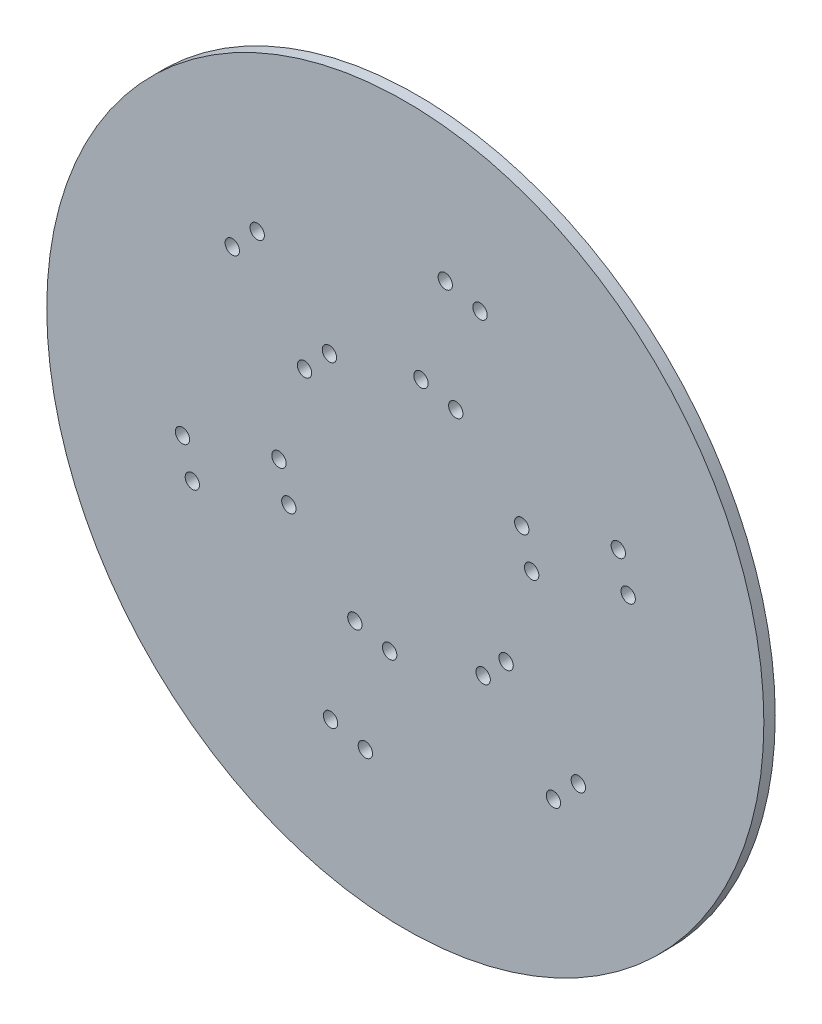
SolidWorks part; units mm, degrees
ref_plane "Front Plane" through (0, 0, 0) normal (0, 0, 1) x (1, 0, 0)
ref_plane "Top Plane" through (0, 0, 0) normal (0, 1, 0) x (1, 0, 0)
ref_plane "Right Plane" through (0, 0, 0) normal (1, 0, 0) x (0, 0, -1)
sketch "Sketch1" plane through (0, 0, 0) normal (0, 0, 1) x (1, 0, 0)
  circle A0 centre (0, 0) radius 100
  dimension "D1" = 200
extrude "Boss-Extrude1" add sketch "Sketch1" along normal blind 3.175
sketch "Sketch2" plane through (0, 0, 3.175) normal (0, 0, 1) x (1, 0, 0)
  line L0 (-71.9351, 69.4647) -> (71.9351, -69.4647) construction
  line L1 (-96.1257, -27.5653) -> (96.1257, 27.5653) construction
  line L2 (-24.1906, -97.03) -> (24.1906, 97.03) construction
  circle A0 centre (0, 0) radius 100 construction
  point P8 (0, 0)
  point P9 (0, 0)
  point P13 (0, 0)
  dimension "D1" = 60
  dimension "D2" = 60
sketch "Sketch6" plane through (0, 0, 3.175) normal (0, 0, 1) x (1, 0, 0)
  circle A0 centre (-11.1425, -62.1505) radius 2
  circle A1 centre (-20.8455, -59.7314) radius 2
  circle A2 centre (-4.3691, -34.9821) radius 2
  circle A3 centre (-14.0721, -32.563) radius 2
  circle A4 centre (48.2526, -40.7249) radius 2
  circle A5 centre (41.3062, -47.9184) radius 2
  circle A6 centre (21.7061, -27.8768) radius 2
  circle A7 centre (28.1108, -21.2748) radius 2
  circle A8 centre (62.1516, 11.813) radius 2
  circle A9 centre (59.3951, 21.4256) radius 2
  circle A10 centre (32.4799, 13.7073) radius 2
  circle A11 centre (35.2364, 4.0947) radius 2
  circle A12 centre (20.8455, 59.7314) radius 2
  circle A13 centre (11.1425, 62.1505) radius 2
  circle A14 centre (4.3691, 34.9821) radius 2
  circle A15 centre (14.0721, 32.563) radius 2
  circle A16 centre (-21.1643, 28.4683) radius 2
  circle A17 centre (-28.1108, 21.2748) radius 2
  circle A18 centre (-48.2526, 40.7249) radius 2
  circle A19 centre (-41.3062, 47.9184) radius 2
  circle A20 centre (-32.4799, -13.7073) radius 2
  circle A21 centre (-35.2364, -4.0947) radius 2
  circle A22 centre (-59.3951, -21.4256) radius 2
  circle A23 centre (-62.1516, -11.813) radius 2
  dimension "D1" = 4
extrude "Cut-Extrude1" cut sketch "Sketch6" against normal through all contours A8 | A9 | A11 | A10 | A15 | A14 | A12 | A13 | A16 | A17 | A19 | A18 | A21 | A20 | A23 | A22 | A2 | A3 | A0 | A1 | A7 | A4 | A5 | A6 region at (-11.1425, -62.1505, 3.175) region at (-20.8455, -59.7314, 3.175) region at (-4.3691, -34.9821, 3.175) region at (-14.0721, -32.563, 3.175) region at (48.2526, -40.7249, 3.175) region at (41.3062, -47.9184, 3.175) region at (21.7061, -27.8768, 3.175) region at (28.1108, -21.2748, 3.175) region at (62.1516, 11.813, 3.175) region at (59.3951, 21.4256, 3.175) region at (32.4799, 13.7073, 3.175) region at (35.2364, 4.0947, 3.175) region at (20.8455, 59.7314, 3.175) region at (11.1425, 62.1505, 3.175) region at (4.3691, 34.9821, 3.175) region at (14.0721, 32.563, 3.175) region at (-21.1643, 28.4683, 3.175) region at (-28.1108, 21.2748, 3.175) region at (-48.2526, 40.7249, 3.175) region at (-41.3062, 47.9184, 3.175) region at (-32.4799, -13.7073, 3.175) region at (-35.2364, -4.0947, 3.175) region at (-59.3951, -21.4256, 3.175) region at (-62.1516, -11.813, 3.175)
